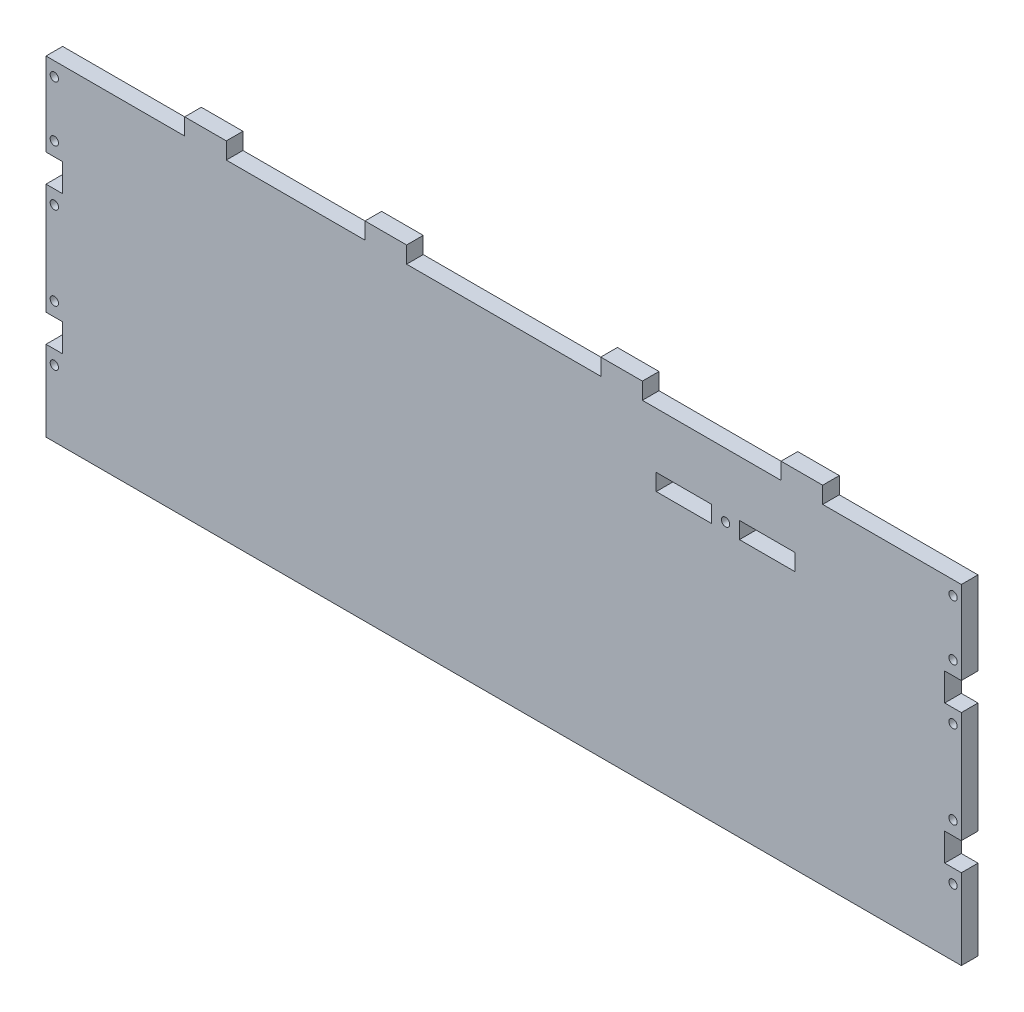
SolidWorks part; units mm, degrees
ref_plane "Plan de face" through (0, 0, 0) normal (0, 0, 1) x (1, 0, 0)
ref_plane "Plan de dessus" through (0, 0, 0) normal (0, 1, 0) x (1, 0, 0)
ref_plane "Plan de droite" through (0, 0, 0) normal (1, 0, 0) x (0, 0, -1)
sketch "Esquisse1" plane through (0, 0, 0) normal (0, 0, 1) x (1, 0, 0)
  line L0 (97.3951, 0) -> (-118.5049, 0) construction
  line L1 (-165, 119) -> (165, 119)
  line L2 (-165, 119) -> (-165, -119)
  line L3 (-165, -119) -> (165, -119)
  line L4 (165, 119) -> (165, -119)
  line L5 (0, 79.3588) -> (0, -79.3588) construction
  line L6 (-92.5, -55) -> (-77.5, -55)
  line L7 (-92.5, -55) -> (-92.5, -61)
  line L8 (-92.5, -61) -> (-77.5, -61)
  line L9 (-77.5, -55) -> (-77.5, -61)
  line L10 (-7.5, -55) -> (7.5, -55)
  line L11 (-7.5, -55) -> (-7.5, -61)
  line L12 (-7.5, -61) -> (7.5, -61)
  line L13 (7.5, -55) -> (7.5, -61)
  line L14 (77.5, -55) -> (92.5, -55)
  line L15 (77.5, -55) -> (77.5, -61)
  line L16 (77.5, -61) -> (92.5, -61)
  line L17 (92.5, -55) -> (92.5, -61)
  line L19 (55, 99) -> (75, 99)
  line L20 (55, 99) -> (55, 93)
  line L21 (55, 93) -> (75, 93)
  line L22 (75, 99) -> (75, 93)
  line L23 (85, 99) -> (105, 99)
  line L24 (85, 99) -> (85, 93)
  line L25 (85, 93) -> (105, 93)
  line L26 (105, 99) -> (105, 93)
  dimension "D1" = 238
  dimension "D2" = 330
  dimension "D3" = 165
  dimension "D4" = 119
  dimension "D5" = 15
  dimension "D6" = 6
  dimension "D7" = 6
  dimension "D8" = 15
  dimension "D9" = 6
  dimension "D10" = 15
  dimension "D11" = 70
  dimension "D12" = 70
  dimension "D13" = 58
  dimension "D14" = 72.5
  dimension "D15" = 6
  dimension "D16" = 20
  dimension "D17" = 20
  dimension "D18" = 6
  dimension "D19" = 10
  dimension "D20" = 60
  dimension "D21" = 20
  dimension "D22" = 20
extrude "Boss.-Extru.1" add sketch "Esquisse1" along normal blind 6
sketch "Esquisse2" plane through (0, 0, 6) normal (0, 0, 1) x (1, 0, 0)
  line L0 (243.146, 0) -> (-260.0003, 0) construction
  line L1 (0, 180.4713) -> (0, -129.6072) construction
  line L2 (165, 119) -> (-165, 119) construction
  line L3 (-115, 119) -> (-100, 119)
  line L4 (-115, 119) -> (-115, 125)
  line L5 (-115, 125) -> (-100, 125)
  line L6 (-100, 119) -> (-100, 125)
  line L7 (-165, 119) -> (-165, -119) construction
  line L8 (-50, 119) -> (-35, 119)
  line L9 (-50, 119) -> (-50, 125)
  line L10 (-50, 125) -> (-35, 125)
  line L11 (-35, 119) -> (-35, 125)
  line L12 (35, 119) -> (35, 125)
  line L13 (50, 125) -> (35, 125)
  line L14 (50, 119) -> (50, 125)
  line L15 (50, 119) -> (35, 119)
  line L16 (100, 119) -> (100, 125)
  line L17 (115, 125) -> (100, 125)
  line L18 (115, 119) -> (115, 125)
  line L19 (115, 119) -> (100, 119)
  line L20 (-115, 119) -> (-100, 119)
  line L21 (-115, 119) -> (-115, 125)
  line L22 (-115, 125) -> (-100, 125)
  line L23 (-100, 119) -> (-100, 125)
  line L24 (-50, 119) -> (-35, 119)
  line L25 (-50, 119) -> (-50, 125)
  line L26 (-50, 125) -> (-35, 125)
  line L27 (-35, 119) -> (-35, 125)
  line L28 (35, 119) -> (35, 125)
  line L29 (50, 125) -> (35, 125)
  line L30 (50, 119) -> (50, 125)
  line L31 (50, 119) -> (35, 119)
  line L32 (100, 119) -> (100, 125)
  line L33 (115, 125) -> (100, 125)
  line L34 (115, 119) -> (115, 125)
  line L35 (115, 119) -> (100, 119)
  line L36 (115, -119) -> (100, -119)
  line L37 (115, -119) -> (115, -125)
  line L38 (115, -125) -> (100, -125)
  line L39 (100, -119) -> (100, -125)
  line L40 (50, -119) -> (35, -119)
  line L41 (50, -119) -> (50, -125)
  line L42 (50, -125) -> (35, -125)
  line L43 (35, -119) -> (35, -125)
  line L44 (-35, -119) -> (-35, -125)
  line L45 (-50, -125) -> (-35, -125)
  line L46 (-50, -119) -> (-50, -125)
  line L47 (-50, -119) -> (-35, -119)
  line L48 (-100, -119) -> (-100, -125)
  line L49 (-115, -125) -> (-100, -125)
  line L50 (-115, -119) -> (-115, -125)
  line L51 (-115, -119) -> (-100, -119)
  line L52 (115, -119) -> (100, -119)
  line L53 (115, -119) -> (115, -125)
  line L54 (115, -125) -> (100, -125)
  line L55 (100, -119) -> (100, -125)
  line L56 (50, -119) -> (35, -119)
  line L57 (50, -119) -> (50, -125)
  line L58 (50, -125) -> (35, -125)
  line L59 (35, -119) -> (35, -125)
  line L60 (-35, -119) -> (-35, -125)
  line L61 (-50, -125) -> (-35, -125)
  line L62 (-50, -119) -> (-50, -125)
  line L63 (-50, -119) -> (-35, -119)
  line L64 (-100, -119) -> (-100, -125)
  line L65 (-115, -125) -> (-100, -125)
  line L66 (-115, -119) -> (-115, -125)
  line L67 (-115, -119) -> (-100, -119)
  line M9 (-165, -119) -> (165, -119)
  line M11 (165, 119) -> (-165, 119)
  dimension "D1" = 6
  dimension "D2" = 6
  dimension "D3" = 15
  dimension "D4" = 15
  dimension "D5" = 50
  dimension "D6" = 50
extrude "Boss.-Extru.2" add sketch "Esquisse2" against normal blind 6 contours L6 L5 L4 M11 | L11 L10 L9 M11 | L14 L13 L12 M11 | L18 L17 L16 M11 | L39 L38 L37 M9 | L43 L42 L41 M9 | L46 L45 L44 M9 | L50 L49 L48 M9 region at (-107.5, 122, 6) region at (107.5, 122, 6) region at (42.5, 122, 6) region at (-42.5, 122, 6) region at (107.5, -122, 6) region at (-107.5, -122, 6) region at (-42.5, -122, 6) region at (42.5, -122, 6)
sketch "Esquisse3" plane through (0, 0, 6) normal (0, 0, 1) x (1, 0, 0)
  line L0 (-165, 119) -> (-165, -119) construction
  line L1 (-165, 79) -> (-159, 79)
  line L2 (-165, 79) -> (-165, 89)
  line L3 (-165, 89) -> (-159, 89)
  line L4 (-159, 79) -> (-159, 89)
  line L5 (234.1368, 0) -> (-337.9213, 0) construction
  line L6 (-165, 39) -> (-159, 39)
  line L7 (-165, 39) -> (-165, 29)
  line L8 (-165, 29) -> (-159, 29)
  line L9 (-159, 39) -> (-159, 29)
  line L10 (0, 279.7488) -> (0, -188.1201) construction
  line L11 (-115, 119) -> (-165, 119) construction
  line L12 (-159, -39) -> (-159, -29)
  line L13 (-165, -29) -> (-159, -29)
  line L14 (-165, -39) -> (-165, -29)
  line L15 (-165, -39) -> (-159, -39)
  line L16 (-159, -79) -> (-159, -89)
  line L17 (-165, -89) -> (-159, -89)
  line L18 (-165, -79) -> (-165, -89)
  line L19 (-165, -79) -> (-159, -79)
  line L20 (165, -79) -> (159, -79)
  line L21 (165, -79) -> (165, -89)
  line L22 (165, -89) -> (159, -89)
  line L23 (159, -79) -> (159, -89)
  line L24 (165, -39) -> (159, -39)
  line L25 (165, -39) -> (165, -29)
  line L26 (165, -29) -> (159, -29)
  line L27 (159, -39) -> (159, -29)
  line L28 (159, 39) -> (159, 29)
  line L29 (165, 29) -> (159, 29)
  line L30 (165, 39) -> (165, 29)
  line L31 (165, 39) -> (159, 39)
  line L32 (159, 79) -> (159, 89)
  line L33 (165, 89) -> (159, 89)
  line L34 (165, 79) -> (165, 89)
  line L35 (165, 79) -> (159, 79)
  line L36 (153, -119) -> (153, -109)
  line L37 (-165, -119) -> (-153, -119)
  line L38 (-165, -119) -> (-165, -109)
  line L39 (-165, -109) -> (-153, -109)
  line L40 (-153, -119) -> (-153, -109)
  line L41 (165, -109) -> (153, -109)
  line L42 (165, -119) -> (165, -109)
  line L43 (165, -119) -> (153, -119)
  dimension "D1" = 40
  dimension "D2" = 6
  dimension "D3" = 6
  dimension "D4" = 10
  dimension "D5" = 10
  dimension "D6" = 30
  dimension "D7" = 12
  dimension "D8" = 10
extrude "Enlèv. mat.-Extru.1" cut sketch "Esquisse3" against normal blind 6
sketch "Esquisse4" plane through (0, 0, 6) normal (0, 0, 1) x (1, 0, 0)
  line L0 (-162, 121.7279) -> (-162, -131.0602) construction
  line L1 (0, 158.5579) -> (0, -182.4489) construction
  line L2 (-115, 119) -> (-165, 119) construction
  line L3 (-106.4439, -58) -> (117.3944, -58) construction
  line L4 (-159, 89) -> (-165, 89) construction
  line L5 (-165, 119) -> (-165, 89) construction
  line L6 (-165, 79) -> (-159, 79) construction
  line L7 (-159, 39) -> (-165, 39) construction
  line L8 (-165, 29) -> (-159, 29) construction
  line L9 (-159, -29) -> (-165, -29) construction
  line L10 (-92.5, -55) -> (-92.5, -61) construction
  line L11 (-77.5, -61) -> (-77.5, -55) construction
  line L12 (-165, -39) -> (-159, -39) construction
  line L13 (-159, -79) -> (-165, -79) construction
  line L14 (-165, -89) -> (-159, -89) construction
  line L15 (-7.5, -55) -> (-7.5, -61) construction
  line L16 (162, 121.7279) -> (162, -131.0602) construction
  line L17 (116.5184, 96) -> (43.4816, 96) construction
  line L21 (75, 93) -> (75, 99) construction
  line L23 (55, 93) -> (75, 93) construction
  circle A0 centre (-162, 114) radius 1.5
  circle A1 centre (-162, 94) radius 1.5
  circle A2 centre (-162, 74) radius 1.5
  circle A3 centre (-162, 44) radius 1.5
  circle A4 centre (-162, 24) radius 1.5
  circle A6 centre (-162, -24) radius 1.5
  circle A7 centre (-162, -44) radius 1.5
  circle A8 centre (-162, -74) radius 1.5
  circle A9 centre (-162, -94) radius 1.5
  circle A10 centre (-97.5, -58) radius 1.5
  circle A11 centre (-72.5, -58) radius 1.5
  circle A12 centre (162, -94) radius 1.5
  circle A13 centre (162, -74) radius 1.5
  circle A14 centre (162, -44) radius 1.5
  circle A15 centre (162, -24) radius 1.5
  circle A16 centre (80, 96) radius 1.5
  circle A17 centre (162, 24) radius 1.5
  circle A18 centre (162, 44) radius 1.5
  circle A19 centre (162, 74) radius 1.5
  circle A20 centre (162, 94) radius 1.5
  circle A21 centre (162, 114) radius 1.5
  circle A22 centre (-12.5, -58) radius 1.5
  circle A23 centre (12.5, -58) radius 1.5
  circle A24 centre (72.5, -58) radius 1.5
  circle A25 centre (97.5, -58) radius 1.5
  dimension "D1" = 3
  dimension "D2" = 3
  dimension "D3" = 3
  dimension "D4" = 3
  dimension "D5" = 3
  dimension "D6" = 3
  dimension "D7" = 3
  dimension "D8" = 3
  dimension "D9" = 3
  dimension "D10" = 3
  dimension "D11" = 3
  dimension "D12" = 5
  dimension "D13" = 5
  dimension "D15" = 5
  dimension "D16" = 5
  dimension "D17" = 5
  dimension "D20" = 5
  dimension "D21" = 5
  dimension "D23" = 3
  dimension "D24" = 3
  dimension "D25" = 5
  dimension "D26" = 5
  dimension "D27" = 5
  dimension "D30" = 5
  dimension "D14" = 3
  dimension "D18" = 5
  dimension "D22" = 5
  dimension "D32" = 3
extrude "Enlèv. mat.-Extru.2" cut sketch "Esquisse4" against normal blind 6
sketch "Esquisse5" plane through (0, 0, 6) normal (0, 0, 1) x (1, 0, 0)
  line L1 (-200.0968, 0) -> (223.5072, 0)
  line L2 (-200.0968, 0) -> (-200.0968, -150.3561)
  line L3 (-200.0968, -150.3561) -> (223.5072, -150.3561)
  line L4 (223.5072, 0) -> (223.5072, -150.3561)
extrude "Enlèv. mat.-Extru.3" cut sketch "Esquisse5" against normal blind 6
equation "\"D3@Esquisse1\"=\"D2@Esquisse1\"/2"
equation "\"D4@Esquisse1\"=\"D1@Esquisse1\"/2"
